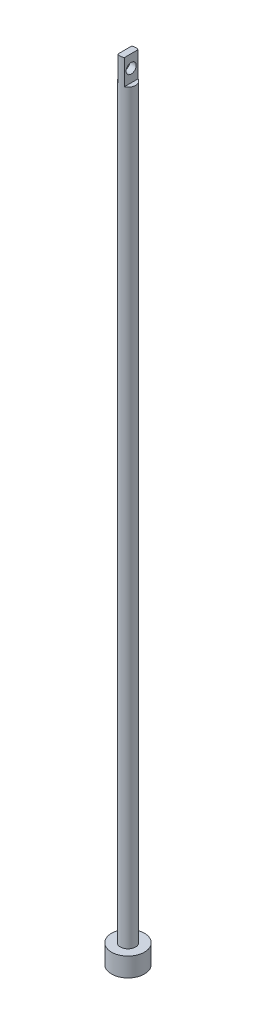
SolidWorks part; units mm, degrees
ref_plane "前视基准面" through (0, 0, 0) normal (0, 0, 1) x (1, 0, 0)
ref_plane "上视基准面" through (0, 0, 0) normal (0, 1, 0) x (1, 0, 0)
ref_plane "右视基准面" through (0, 0, 0) normal (1, 0, 0) x (0, 0, -1)
sketch "草图1" plane through (0, 0, 0) normal (0, 1, 0) x (1, 0, 0)
  circle A0 centre (0, 0) radius 13
  dimension "D1" = 26
extrude "凸台-拉伸1" add sketch "草图1" along normal blind 15
sketch "草图2" plane through (0, 15, 0) normal (0, 1, 0) x (1, 0, 0)
  circle A0 centre (0, 0) radius 6
  dimension "D1" = 12
extrude "凸台-拉伸2" add sketch "草图2" along normal blind 610
sketch "草图3" plane through (0, 625, 0) normal (0, 1, 0) x (1, 0, 0)
  line L1 (-2.5, 10) -> (2.5, 10)
  line L2 (-2.5, 10) -> (-2.5, -10)
  line L3 (-2.5, -10) -> (2.5, -10)
  line L4 (2.5, 10) -> (2.5, -10)
  line L5 (-2.5, 10) -> (2.5, -10) construction
  line L6 (-2.5, -10) -> (2.5, 10) construction
  point P0 (0, 0)
  point P1 (0, 0)
  dimension "D1" = 5
  dimension "D2" = 20
extrude "切除-拉伸1" cut sketch "草图3" against normal blind 20 flip side to cut
ref_plane "基准面1" through (-2.5, 0, 0) normal (-1, 0, 0) x (0, 0, 1)
sketch "草图4" plane through (-2.5, 0, 0) normal (-1, 0, 0) x (0, 0, 1)
  line L0 (0, 0) -> (0, 362.7684) construction
  line L4 (-5.4544, 615) -> (5.4544, 615)
  line L5 (-5.4544, 615) -> (5.4544, 615) construction
  circle A0 centre (0, 615) radius 4
  point P8 (0, 615)
  dimension "D2" = 8
  dimension "D1" = 10
extrude "切除-拉伸2" cut sketch "草图4" against normal blind 20
